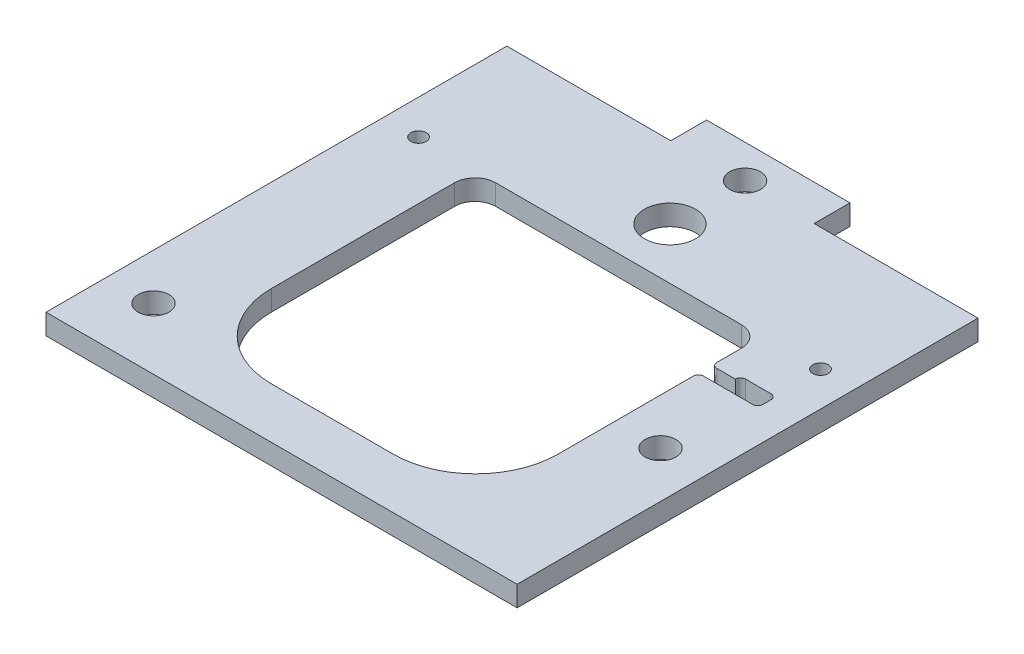
SolidWorks part; units mm, degrees
material "Thornel Mat VMA"
ref_plane "Front Plane" through (0, 0, 0) normal (0, 0, 1) x (1, 0, 0)
ref_plane "Top Plane" through (0, 0, 0) normal (0, 1, 0) x (1, 0, 0)
ref_plane "Right Plane" through (0, 0, 0) normal (1, 0, 0) x (0, 0, -1)
sketch "Sketch1" plane through (0, 0, 0) normal (0, 1, 0) x (1, 0, 0)
  line L0 (0, 0) -> (0, 45) construction
  line L1 (-23, 0) -> (23, 0)
  line L2 (23, 0) -> (23, 45)
  line L3 (7, 45) -> (7, 48.5)
  line L4 (7, 48.5) -> (-7, 48.5)
  line L5 (-7, 48.5) -> (-7, 45)
  line L6 (-23, 0) -> (-23, 45)
  line L7 (-23, 45) -> (-7, 45)
  line L8 (7, 45) -> (23, 45)
  circle A0 centre (-18.5, 6) radius 1.5
  circle A1 centre (18.5, 18.5) radius 1.5
  point P11 (0, 0)
  dimension "D4" = 3
  dimension "D1" = 46
  dimension "D2" = 4.5
  dimension "D3" = 6
  dimension "D5" = 45
  dimension "D6" = 4.5
  dimension "D7" = 12.5
  dimension "D8" = 14
  dimension "D9" = 3.5
extrude "Extrude1" add sketch "Sketch1" along normal blind 2
sketch "Sketch2" plane through (0, 2, 0) normal (0, 1, 0) x (1, 0, 0)
  line L0 (-5.95, 4.95) -> (5.95, 4.95)
  line L1 (-14, 32.9) -> (14, 32.9)
  line L2 (-23, 0) -> (23, 0) construction
  line L3 (0, 0) -> (0, 45) construction
  line L4 (9.05, 13) -> (9.05, 21.5) construction
  line L5 (-7.05, 13) -> (-7.05, 21.5) construction
  line L6 (-23, 45) -> (-7, 45) construction
  line L7 (14, 32.9) -> (14, 13)
  line L8 (14, 21.5) -> (9.05, 21.5) construction
  line L9 (23, 0) -> (23, 45) construction
  line L10 (-14, 32.9) -> (-14, 13)
  line L11 (-14, 21.5) -> (-7.05, 21.5) construction
  line L12 (-23, 0) -> (-23, 45) construction
  arc A0 (-14, 13) -> (-5.95, 4.95) centre (-5.95, 13) ccw
  arc A1 (-7.05, 13) -> (9.05, 13) centre (1, 13) ccw construction
  arc A2 (14, 13) -> (5.95, 4.95) centre (5.95, 13) cw
  dimension "D3" = 8.05
  dimension "D1" = 13
  dimension "D2" = 1
  dimension "D4" = 12.1
  dimension "D5" = 3
  dimension "D6" = 9
  dimension "D7" = 9
extrude "Cut-Extrude1" cut sketch "Sketch2" against normal blind 2
fillet "Fillet1" radius 2 2 edges at (-14, 1, -32.9) (14, 1, -32.9)
sketch "Sketch3" plane through (0, 2, 0) normal (0, 1, 0) x (1, 0, 0)
  line L0 (0, 0) -> (0, 55.7903) construction
  line L2 (7, 48.5) -> (-7, 48.5) construction
  line L3 (14, 42.675) -> (14, 33.175) construction
  line L5 (14, 37.925) -> (0, 37.925) construction
  circle A1 centre (0, 45.2579) radius 1.5
  circle A2 centre (-19.625, 33) radius 0.75
  circle A4 centre (19.625, 33) radius 0.75
  circle A5 centre (0, 37.925) radius 2.5
  dimension "D2" = 7.3329
  dimension "D4" = 3
  dimension "D1" = 5
  dimension "D7" = 1.5
  dimension "D3" = 4.925
  dimension "D5" = 3.2421
  dimension "D6" = 39.25
extrude "Cut-Extrude3" cut sketch "Sketch3" against normal up to next
sketch "Sketch10" plane through (0, 2, 0) normal (0, 1, 0) x (1, 0, 0)
  line L0 (14, 26.7) -> (19.8, 26.7)
  line L2 (19.8, 26.7) -> (19.8, 28.5)
  line L3 (19.8, 28.5) -> (16.3, 28.5)
  line L4 (16.3, 28.5) -> (16.3, 28)
  line L5 (16.3, 28) -> (14, 28)
  line L7 (14, 28) -> (14, 26.7)
  line L8 (14, 13) -> (14, 30.9) construction
  line L10 (20.6, 29.3) -> (15.5, 29.3) construction
  line L11 (18.05, 29.3) -> (18.05, 26.7) construction
  line L14 (18.05, 28) -> (18.7131, 28) construction
  line L15 (-23, 0) -> (23, 0) construction
  dimension "D1" = 1.3
  dimension "D2" = 3.5
  dimension "D3" = 1
  dimension "D4" = 26.7
  dimension "D5" = 2.6
  dimension "D6" = 5.8
extrude "Cut-Extrude4" cut sketch "Sketch10" against normal up to next
fillet "Fillet2" radius 0.5 5 edges at (16.3, 1, -28.5) (19.8, 1, -28.5) (19.8, 1, -26.7) (14, 1, -28) (14, 1, -26.7)
sketch "Sketch9" plane through (0, 0, 0) normal (0, -1, 0) x (1, 0, 0)
  line L0 (-5.95, -4.95) -> (5.95, -4.95) construction
  line L1 (-14, -30.9) -> (-14, -13) construction
  line L2 (12, -32.9) -> (-12, -32.9) construction
  line L4 (-5.95, -4.95) -> (5.95, -4.95)
  line L5 (-14, -30.9) -> (-14, -13)
  line L6 (12, -32.9) -> (-12, -32.9)
  line L7 (14, -13) -> (14, -26.2) construction
  line L8 (23, -45) -> (23, 0)
  line L9 (23, 0) -> (-23, 0)
  line L10 (-23, 0) -> (-23, -45)
  line L11 (-23, -45) -> (-7, -45)
  line L12 (-7, -45) -> (-7, -48.5)
  line L13 (-7, -48.5) -> (7, -48.5)
  line L14 (7, -48.5) -> (7, -45)
  line L15 (7, -45) -> (23, -45)
  line L16 (23, -45) -> (23, 0)
  line L17 (23, 0) -> (-23, 0)
  line L18 (-23, 0) -> (-23, -45)
  line L19 (-23, -45) -> (-7, -45)
  line L20 (-7, -45) -> (-7, -48.5)
  line L21 (-7, -48.5) -> (7, -48.5)
  line L22 (7, -48.5) -> (7, -45)
  line L23 (7, -45) -> (23, -45)
  line L24 (14, -13) -> (14, -26.2)
  line L25 (14.5, -26.7) -> (19.3, -26.7) construction
  line L26 (14.5, -26.7) -> (19.3, -26.7)
  line L27 (19.8, -27.2) -> (19.8, -28) construction
  line L28 (19.8, -27.2) -> (19.8, -28)
  line L29 (19.3, -28.5) -> (16.8, -28.5) construction
  line L30 (19.3, -28.5) -> (16.8, -28.5)
  line L31 (16.3, -28) -> (14.5, -28) construction
  line L32 (16.3, -28) -> (14.5, -28)
  line L33 (14, -28.5) -> (14, -30.9) construction
  line L34 (14, -28.5) -> (14, -30.9)
  arc A0 (-5.95, -4.95) -> (-14, -13) centre (-5.95, -13) ccw construction
  arc A1 (-14, -30.9) -> (-12, -32.9) centre (-12, -30.9) ccw construction
  arc A2 (12, -32.9) -> (14, -30.9) centre (12, -30.9) ccw construction
  arc A3 (14, -13) -> (5.95, -4.95) centre (5.95, -13) ccw construction
  arc A4 (-5.95, -4.95) -> (-14, -13) centre (-5.95, -13) ccw
  arc A5 (-14, -30.9) -> (-12, -32.9) centre (-12, -30.9) ccw
  arc A6 (12, -32.9) -> (14, -30.9) centre (12, -30.9) ccw
  arc A7 (14, -13) -> (5.95, -4.95) centre (5.95, -13) ccw
  arc A8 (14, -26.2) -> (14.5, -26.7) centre (14.5, -26.2) ccw construction
  arc A11 (14, -26.2) -> (14.5, -26.7) centre (14.5, -26.2) ccw
  arc A13 (19.8, -27.2) -> (19.3, -26.7) centre (19.3, -27.2) ccw construction
  arc A15 (19.8, -27.2) -> (19.3, -26.7) centre (19.3, -27.2) ccw
  arc A16 (19.3, -28.5) -> (19.8, -28) centre (19.3, -28) ccw construction
  circle A17 centre (-18.5, -6) radius 0.8
  circle A18 centre (18.5, -18.5) radius 0.8
  circle A19 centre (19.625, -33) radius 0.8
  circle A20 centre (0, -37.925) radius 0.8
  circle A21 centre (0, -45.2579) radius 0.8
  circle A22 centre (-19.625, -33) radius 0.8
  arc A23 (19.3, -28.5) -> (19.8, -28) centre (19.3, -28) ccw
  circle A24 centre (19.625, -33) radius 0.75 construction
  circle A25 centre (-19.625, -33) radius 0.75 construction
  arc A26 (16.3, -28) -> (16.8, -28.5) centre (16.8, -28) ccw construction
  arc A27 (16.3, -28) -> (16.8, -28.5) centre (16.8, -28) ccw
  arc A28 (14.5, -28) -> (14, -28.5) centre (14.5, -28.5) ccw construction
  arc A29 (14.5, -28) -> (14, -28.5) centre (14.5, -28.5) ccw
  dimension "D2" = 1.6
  dimension "D1" = 0
extrude "Boss-Extrude1" [suppressed] add sketch "Sketch9" along normal blind 1 separate body
